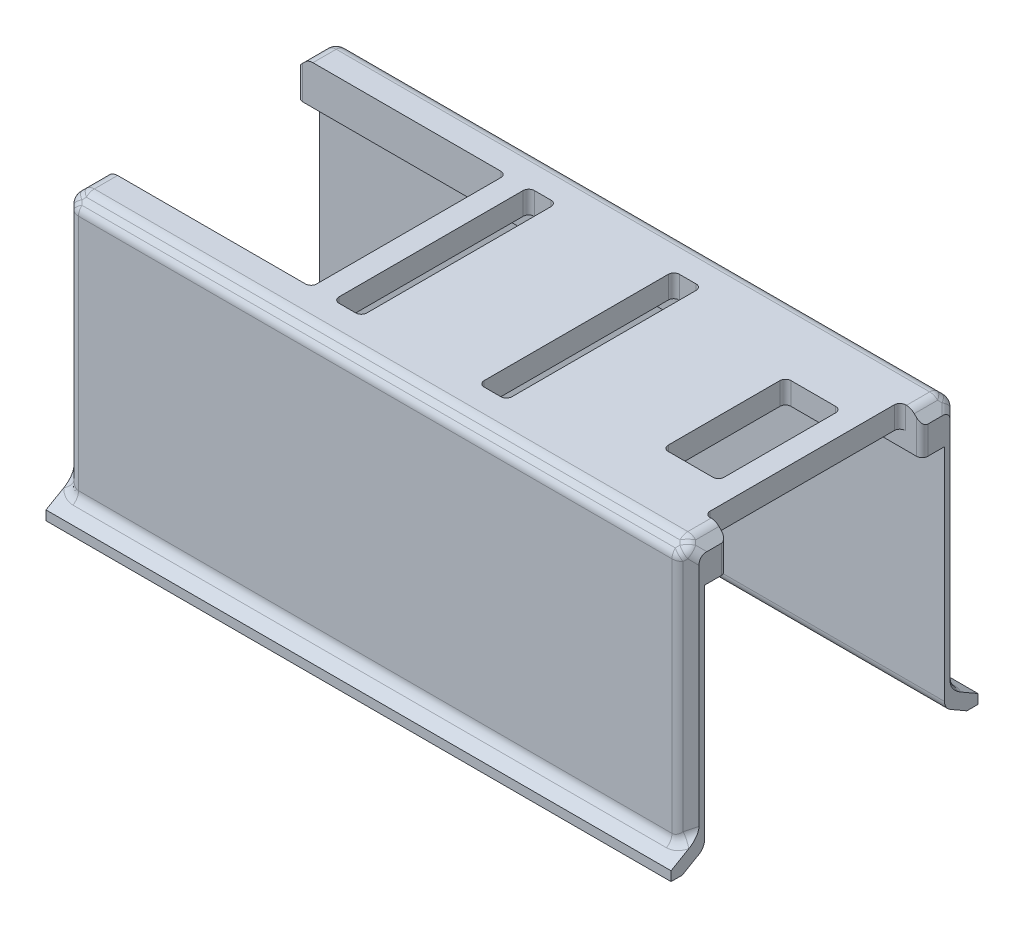
SolidWorks part; units mm, degrees
note: The reader was unsure of these and kept them because the rebuilt part matched: shared geometry of "Sketch1<4>", "Sketch1<5>", "Sketch1<6>".
ref_plane "Front Plane" through (0, 0, 0) normal (0, 0, 1) x (1, 0, 0)
ref_plane "Top Plane" through (0, 0, 0) normal (0, 1, 0) x (1, 0, 0)
ref_plane "Right Plane" through (0, 0, 0) normal (1, 0, 0) x (0, 0, -1)
sketch "Sketch1" plane through (0, 0, 0) normal (0, 1, 0) x (1, 0, 0)
  line L0 (0, 0) -> (180.9202, 0) construction
  line L5 (0, 0) -> (0, 116.8777) construction
  line L6 (33.75, 8.75) -> (36.25, 8.75) construction
  line L7 (0, 10.75) -> (56, 10.75) construction
  line L8 (0, 10.75) -> (0, -10.75) construction
  line L9 (0, -10.75) -> (56, -10.75) construction
  line L10 (56, 10.75) -> (56, -10.75) construction
  line L11 (20.75, 8.75) -> (23.25, 8.75) construction
  line L12 (20.75, 8.75) -> (20.75, -8.75) construction
  line L13 (20.75, -8.75) -> (23.25, -8.75) construction
  line L14 (23.25, 8.75) -> (23.25, -8.75) construction
  line L15 (33.75, 8.75) -> (33.75, -8.75) construction
  line L16 (33.75, -8.75) -> (36.25, -8.75) construction
  line L17 (36.25, 8.75) -> (36.25, -8.75) construction
  line L18 (0, -8.75) -> (56, -8.75)
  line L19 (47, 5.5) -> (52, 5.5) construction
  line L20 (47, 5.5) -> (47, -5.5) construction
  line L21 (47, -5.5) -> (52, -5.5) construction
  line L22 (52, 5.5) -> (52, -5.5) construction
  line L23 (0, 10.75) -> (56, 10.75)
  line L24 (0, 10.75) -> (0, 8.75)
  line L25 (0, 8.75) -> (56, 8.75)
  line L26 (56, 10.75) -> (56, 8.75)
  line L27 (56, -10.75) -> (56, -8.75)
  line L28 (0, -10.75) -> (56, -10.75)
  line L29 (0, -10.75) -> (0, -8.75)
  line L30 (0, -10.75) -> (56, -10.75)
  line L31 (18.75, 8.75) -> (20.75, 8.75)
  line L32 (18.75, 8.75) -> (18.75, -8.75)
  line L33 (18.75, -8.75) -> (20.75, -8.75)
  line L34 (20.75, 8.75) -> (20.75, -8.75)
  line L35 (23.25, 8.75) -> (33.75, 8.75)
  line L36 (23.25, 8.75) -> (23.25, -8.75)
  line L37 (23.25, -8.75) -> (33.75, -8.75)
  line L38 (33.75, 8.75) -> (33.75, -8.75)
  line L39 (36.25, 8.75) -> (54, 8.75)
  line L40 (36.25, 8.75) -> (36.25, -8.75)
  line L41 (36.25, -8.75) -> (54, -8.75)
  line L42 (54, 8.75) -> (54, -8.75)
  line L43 (47, 5.5) -> (52, 5.5)
  line L44 (47, 5.5) -> (47, -5.5)
  line L45 (47, -5.5) -> (52, -5.5)
  line L46 (52, 5.5) -> (52, -5.5)
  line L47 (0, 12.25) -> (56, 12.25)
  line L48 (0, 12.25) -> (0, 10.75)
  line L49 (0, 10.75) -> (56, 10.75)
  line L50 (56, 12.25) -> (56, 10.75)
  line L51 (56, -12.25) -> (56, -10.75)
  line L52 (0, -12.25) -> (56, -12.25)
  line L53 (0, -12.25) -> (0, -10.75)
  line L54 (0, -12.25) -> (56, -12.25)
  line L55 (0, 13.75) -> (56, 13.75)
  line L56 (0, 13.75) -> (0, 12.25)
  line L57 (0, 12.25) -> (56, 12.25)
  line L58 (56, 13.75) -> (56, 12.25)
  line L59 (56, -13.75) -> (56, -12.25)
  line L60 (0, -13.75) -> (56, -13.75)
  line L61 (0, -13.75) -> (0, -12.25)
  dimension "D1" = 21.5
  dimension "D2" = 56
  dimension "D3" = 17.5
  dimension "D4" = 2.5
  dimension "D5" = 20.75
  dimension "D6" = 33.75
  dimension "D7" = 2.5
  dimension "D8" = 47
  dimension "D9" = 5
  dimension "D10" = 11
  dimension "D11" = 2
  dimension "D12" = 2
  dimension "D13" = 2
  dimension "D14" = 1.5
  dimension "D15" = 1.5
extrude "Boss-Extrude1" add sketch "Sketch1" along normal blind 3.5 contours L26 L23 L24 L25 | L29 L28 L27 L18 | L50 L47 L48 L23 | L53 L52 L51 L28
extrude "Boss-Extrude2" add sketch "Sketch1<4>" along normal up to surface (2 mm away) from offset 1.5 contours L34 L25 L32 L18 | L38 L25 L36 L18 | L42 L25 L40 L18 L43 L46 L45 L44
sketch "Sketch1<4>" plane through (0, 0, 0) normal (0, 1, 0) x (1, 0, 0) same geometry as "Sketch1"
extrude "Boss-Extrude3" add sketch "Sketch1<5>" against normal blind 21.5 contours L53 L52 L51 L28 | L50 L47 L48 L23
sketch "Sketch1<5>" plane through (0, 0, 0) normal (0, 1, 0) x (1, 0, 0) same geometry as "Sketch1"
extrude "Boss-Extrude4" add sketch "Sketch1<6>" along normal blind 2 from offset 21.5 contours L61 L60 L59 L52 | L58 L55 L56 L47 offset against normal yes
sketch "Sketch1<6>" plane through (0, 0, 0) normal (0, 1, 0) x (1, 0, 0) same geometry as "Sketch1"
chamfer "Chamfer1" distance 1 angle 45 6 edges at (56, 3.5, -10.5) (28, 3.5, -12.25) (0, 3.5, -10.5) (56, 3.5, 10.5) (0, 3.5, 10.5) (28, 3.5, 12.25)
chamfer "Chamfer2" distance 2 angle 30 4 edges at (28, -19.5, 13.75) (28, -19.5, -13.75) (28, -21.5, 10.75) (28, -21.5, -10.75)
chamfer "Chamfer3" distance 1 angle 45 4 edges at (56, -8.6443, 12.25) (0, -8.6443, 12.25) (0, -8.6443, -12.25) (56, -8.6443, -12.25)
fillet "Fillet1" radius 1 32 edges at (0.75, 2.75, 12) (0.75, 3.25, 11.5) (28, 3.5, 11.25) (55.25, 3.25, 11.5) (55.25, 2.75, 12) (55.25, 2.75, -12) (55.25, 3.25, -11.5) (28, 3.5, -11.25) (0.75, 3.25, -11.5) (0.75, 2.75, -12) (55, -8.6443, -12.25) (28, 2.5, -12.25) (1, -8.6443, -12.25) (28, -19.7887, -12.25) (1, -8.6443, 12.25) (28, 2.5, 12.25) (55, -8.6443, 12.25) (28, -19.7887, 12.25) (1, 3.5, 10) (55.75, 2.75, -11.5) (55.75, 2.75, 11.5) (0.25, 2.75, 11.5) (1, 3.5, -10) (0.25, 2.75, -11.5) (55, 3.5, 10) (55, 3.5, -10) (0.5, -19.5, 11.75) (55.5, -19.5, 11.75) (55.5, -19.5, -11.75) (0.5, -19.5, -11.75) (28, -20.3453, 10.75) (28, -20.3453, -10.75)
fillet "Fillet2" radius 0.5 20 edges at (54, 2.5, -8.75) (54, 2.5, 8.75) (20.75, 2.5, 8.75) (23.25, 2.5, 8.75) (18.75, 2.5, 8.75) (18.75, 2.5, -8.75) (23.25, 2.5, -8.75) (20.75, 2.5, -8.75) (36.25, 2.5, 8.75) (33.75, 2.5, 8.75) (36.25, 2.5, -8.75) (33.75, 2.5, -8.75) (47, 2.5, -5.5) (47, 2.5, 5.5) (52, 2.5, 5.5) (52, 2.5, -5.5) (56, 1.25, -8.75) (56, 1.25, 8.75) (0, 1.25, 8.75) (0, 1.25, -8.75)
